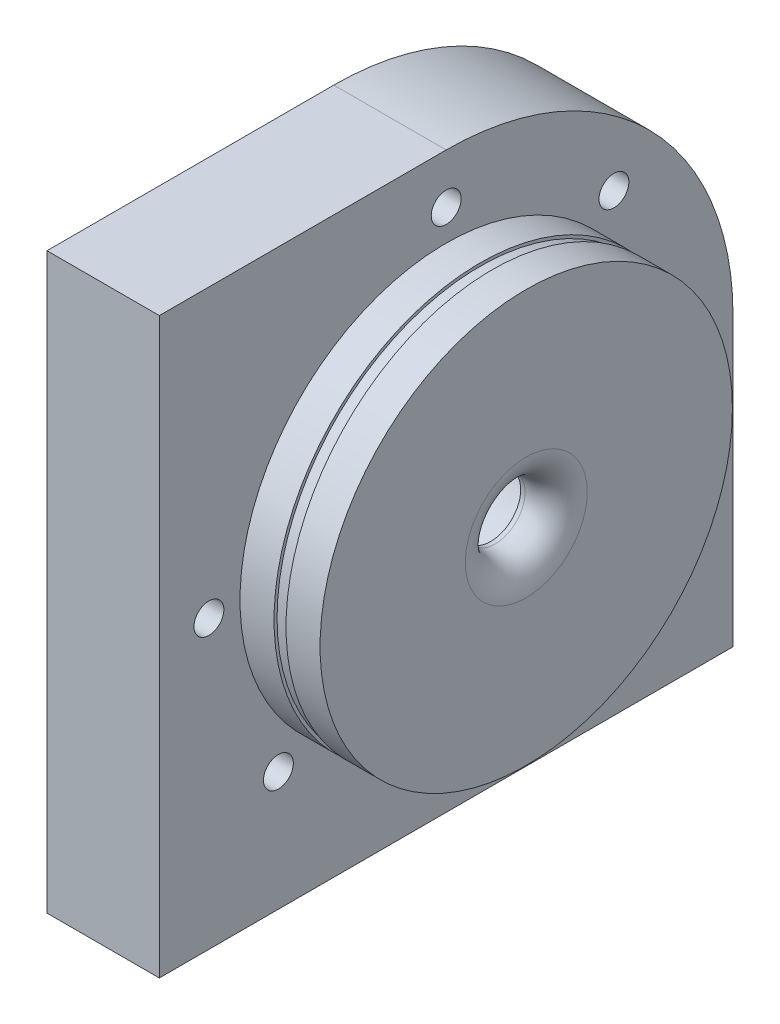
SolidWorks part; units mm, degrees
ref_plane "Front Plane" through (0, 0, 0) normal (0, 0, 1) x (1, 0, 0)
ref_plane "Top Plane" through (0, 0, 0) normal (0, 1, 0) x (1, 0, 0)
ref_plane "Right Plane" through (0, 0, 0) normal (1, 0, 0) x (0, 0, -1)
sketch "Sketch1" plane through (0, 0, 0) normal (1, 0, 0) x (0, 0, -1)
  circle A0 centre (0, 0) radius 43.815
extrude "Housing Fitting Extrude" add sketch "Sketch1" along normal blind 17.018
sketch "Sketch2" plane through (0, 0, 0) normal (-1, 0, 0) x (0, 0, 1)
  line L0 (60.96, 0) -> (60.96, 60.96)
  line L1 (60.96, 60.96) -> (0, 60.96)
  line L2 (60.96, 0) -> (60.96, -54.61)
  line L3 (60.96, -60.96) -> (-60.96, -60.96)
  line L7 (0, -55) -> (0, 55) construction
  line L11 (-60.96, 0) -> (-60.96, -54.61)
  line L12 (60.96, -60.96) -> (60.96, -54.61)
  line L13 (-60.96, -60.96) -> (-60.96, -54.61)
  arc A0 (0, 60.96) -> (-60.96, 0) centre (0, 0) ccw
extrude "Housing Body 1" add sketch "Sketch2" along normal blind 23.876 contours A0 L11 L13 L3 L12 L2 L0 L1
sketch "Sketch3" plane through (17.018, 0, 0) normal (1, 0, 0) x (0, 0, -1)
  circle A0 centre (0, 0) radius 6.35
extrude "Impeller Bore" cut sketch "Sketch3" against normal blind 17.018
sketch "Sketch4" plane through (0, 0, 0) normal (1, 0, 0) x (0, 0, -1)
  circle A0 centre (0, 0) radius 4
extrude "Shaft Bore" cut sketch "Sketch4" against normal blind 70.612
ref_plane "O-Ring Sketch Plane" through (8.509, 0, 0) normal (1, 0, 0) x (0, 0, -1)
sketch "Sketch5" plane through (8.509, 0, 0) normal (1, 0, 0) x (0, 0, -1)
  circle A0 centre (0, 0) radius 43.942
  circle A1 centre (0, 0) radius 43.18
extrude "O-Ring Cut" cut sketch "Sketch5" against normal blind 1.27 and the other way blind 1.27
sketch "Sketch8" plane through (-23.876, 0, 0) normal (-1, 0, 0) x (0, 0, 1)
  circle A1 centre (52.959, 0) radius 3.175
extrude "Fastening Bore" [suppressed] cut sketch "Sketch8" against normal blind 19.05
sketch "Sketch10" plane through (0, 0, 60.96) normal (0, 0, 1) x (1, 0, 0)
  line L0 (0, -60.96) -> (0, 60.96) construction
  line L1 (-23.876, 60.96) -> (0, 60.96)
  line L2 (-23.876, 60.96) -> (-23.876, 10.16)
  line L3 (-23.876, 10.16) -> (0, 10.16)
  line L4 (0, 60.96) -> (0, 10.16)
extrude "Discharge Cut" [suppressed] cut sketch "Sketch10" against normal blind 10.541
sketch "Sketch12" plane through (0, 0, 0) normal (1, 0, 0) x (0, 0, -1)
  circle A0 centre (-50.419, 0) radius 3.175
extrude "Cut-Extrude2" cut sketch "Sketch12" against normal blind 32.004
pattern_circular "CirPattern1" count 8 over 360 of "Cut-Extrude2"
sketch "Sketch13" plane through (0, 0, 60.96) normal (0, 0, 1) x (1, 0, 0)
  circle A1 centre (-9.525, -41.8177) radius 3.175
extrude "Cut-Extrude3" [suppressed] cut sketch "Sketch13" against normal blind 16.51
sketch "Sketch14" plane through (0, -60.96, 0) normal (0, -1, 0) x (1, 0, 0)
  circle A0 centre (-9.525, -46.7543) radius 3.175
  circle A1 centre (-9.525, 41.9141) radius 3.3928
extrude "Cut-Extrude4" cut sketch "Sketch14" against normal blind 16.51
sketch "Sketch15" plane through (0, 0, -60.96) normal (0, 0, -1) x (-1, 0, 0)
  circle A0 centre (9.525, -39.3375) radius 3.175
extrude "Cut-Extrude5" cut sketch "Sketch15" against normal blind 10.922
fillet "Fillet1" radius 6.604 1 edges at (17.018, 0, -6.35)
sketch "Sketch16" plane through (-23.876, 0, 0) normal (-1, 0, 0) x (0, 0, 1)
  circle A0 centre (0, 0) radius 12.954
extrude "Cut-Extrude7" cut sketch "Sketch16" against normal blind 33.3629
sketch "Sketch17" plane through (-23.876, 0, 0) normal (-1, 0, 0) x (0, 0, 1)
  circle A0 centre (0, 0) radius 15.24
extrude "Cut-Extrude8" cut sketch "Sketch17" against normal blind 13.97
sketch "Sketch18" plane through (0, 60.96, 0) normal (0, 1, 0) x (1, 0, 0)
  circle A0 centre (-13.4538, -7.8664) radius 0.7265
extrude "Cut-Extrude9" [suppressed] cut sketch "Sketch18" against normal blind 58.166
sketch "Sketch19" plane through (0, 60.96, 0) normal (0, 1, 0) x (1, 0, 0)
  circle A0 centre (-13.2089, -8.2248) radius 4.7625
extrude "Cut-Extrude10" [suppressed] cut sketch "Sketch19" against normal blind 7.62
sketch "Sketch20" plane through (-23.876, 0, 0) normal (-1, 0, 0) x (0, 0, 1)
  circle A0 centre (0, 0) radius 25.146
extrude "Cut-Extrude11" cut sketch "Sketch20" against normal blind 6.35
